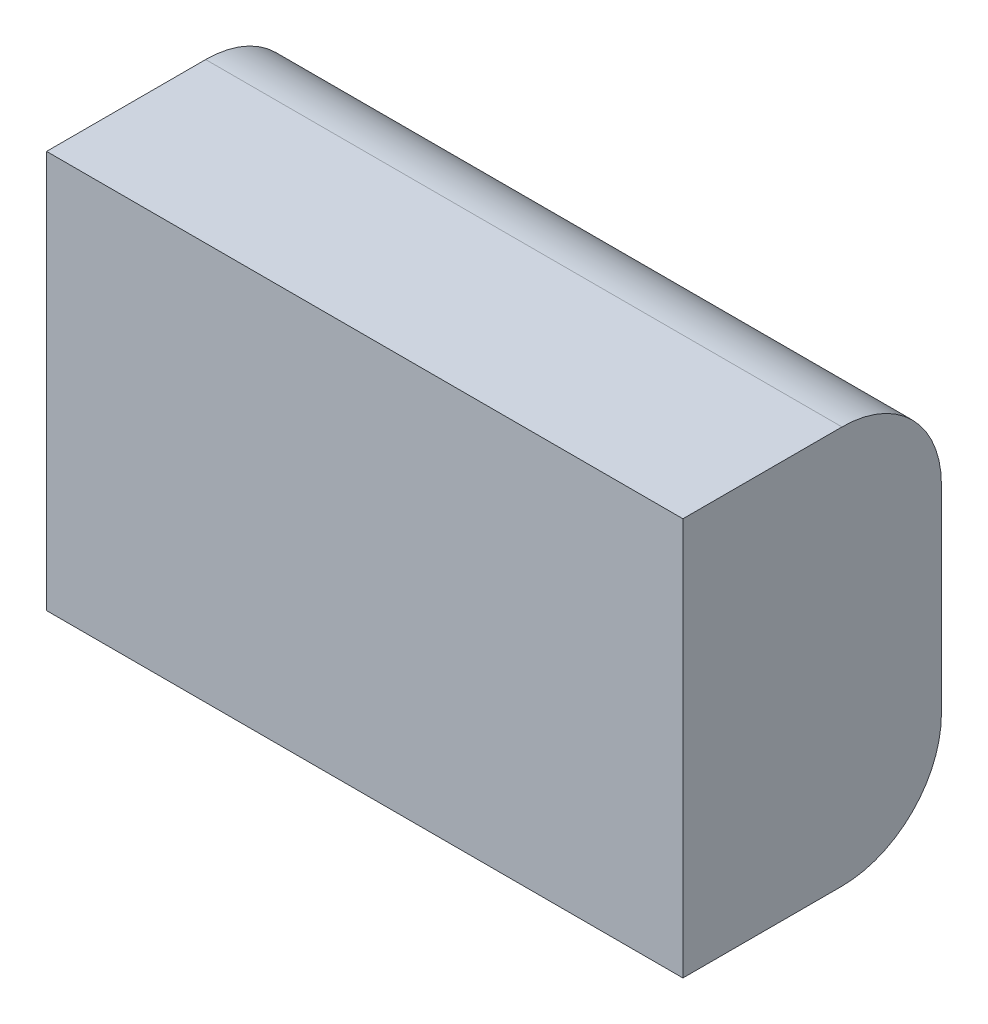
SolidWorks part; units mm, degrees
ref_plane "Front Plane" through (0, 0, 0) normal (0, 0, 1) x (1, 0, 0)
ref_plane "Top Plane" through (0, 0, 0) normal (0, 1, 0) x (1, 0, 0)
ref_plane "Right Plane" through (0, 0, 0) normal (1, 0, 0) x (0, 0, -1)
sketch "Sketch1" plane through (0, 0, 0) normal (1, 0, 0) x (0, 0, -1)
  line L1 (49.3736, 66.0217) -> (-1.4264, 66.0217)
  line L2 (81.1236, 34.2717) -> (81.1236, -29.2283)
  line L3 (49.3736, -60.9783) -> (-1.4264, -60.9783)
  line L4 (-1.4264, 66.0217) -> (-1.4264, -60.9783)
  arc A0 (49.3736, 66.0217) -> (81.1236, 34.2717) centre (49.3736, 34.2717) cw
  arc A1 (81.1236, -29.2283) -> (49.3736, -60.9783) centre (49.3736, -29.2283) cw
  point P8 (81.1236, -60.9783)
  dimension "D3" = 31.75
  dimension "D1" = 127
extrude "Boss-Extrude1" add sketch "Sketch1" along normal mid plane 203.2
equation "\"bumple\"= 24in'bumpler length"
equation "\"D1@Boss-Extrude1\"=\"bumple\""
